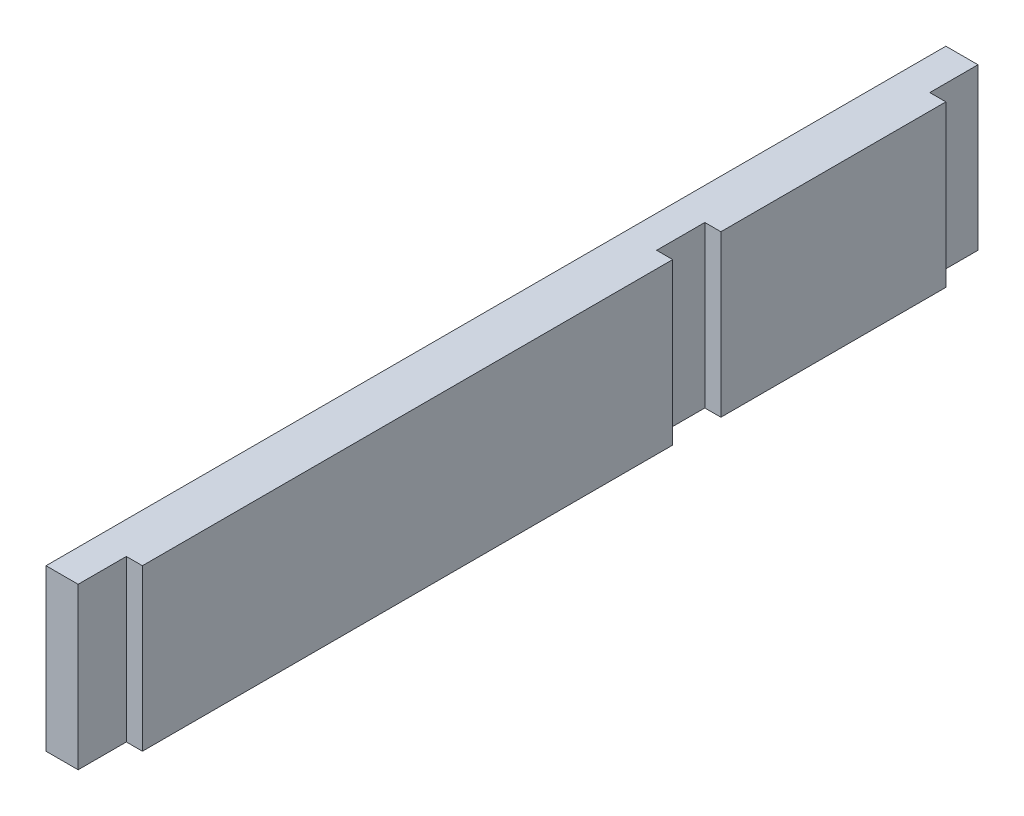
SolidWorks part; units mm, degrees
note: '?' marks a value the reader was unsure of.
material "Mahogany"
ref_plane "Front Plane" through (0, 0, 0) normal (0, 0, 1) x (1, 0, 0)
ref_plane "Top Plane" through (0, 0, 0) normal (0, 1, 0) x (1, 0, 0)
ref_plane "Right Plane" through (0, 0, 0) normal (1, 0, 0) x (0, 0, -1)
ref_axis "X-Axis" through (-88.99, 0, 0) along (1, 0, 0)?
ref_axis "Y-Axis" through (0, 55, 0) along (0, -1, 0)?
ref_axis "Z-Axis" through (0, 0, -88.99) along (0, 0, 1)?
sketch "Sketch2" plane through (0, 0, 0) normal (0, 1, 0) x (1, 0, 0)
  line L0 (-171.45, 88.9) -> (-171.45, -88.9) construction
  line L1 (-171.45, 88.9) -> (-171.45, -88.9)
  line L2 (-171.45, 88.9) -> (-165.1, 88.9)
  line L3 (-165.1, 88.9) -> (-165.1, 79.375)
  line L4 (-165.1, 79.375) -> (-161.925, 79.375)
  line L5 (-161.925, 79.375) -> (-161.925, 34.925)
  line L6 (-161.925, 34.925) -> (-165.1, 34.925)
  line L7 (-165.1, 34.925) -> (-165.1, 25.4)
  line L8 (-165.1, 25.4) -> (-161.925, 25.4)
  line L9 (-161.925, 25.4) -> (-161.925, -79.375)
  line L10 (-161.925, -79.375) -> (-165.1, -79.375)
  line L11 (-165.1, -79.375) -> (-165.1, -88.9)
  line L12 (171.45, -88.9) -> (-171.45, -88.9) construction
  line L13 (-165.1, -88.9) -> (-165.1, -79.375) construction
  line L14 (-165.1, -88.9) -> (-171.45, -88.9)
extrude "Boss-Extrude1" add sketch "Sketch2" along normal up to vertex (15.875 mm away) and the other way up to vertex (15.875 mm away)
